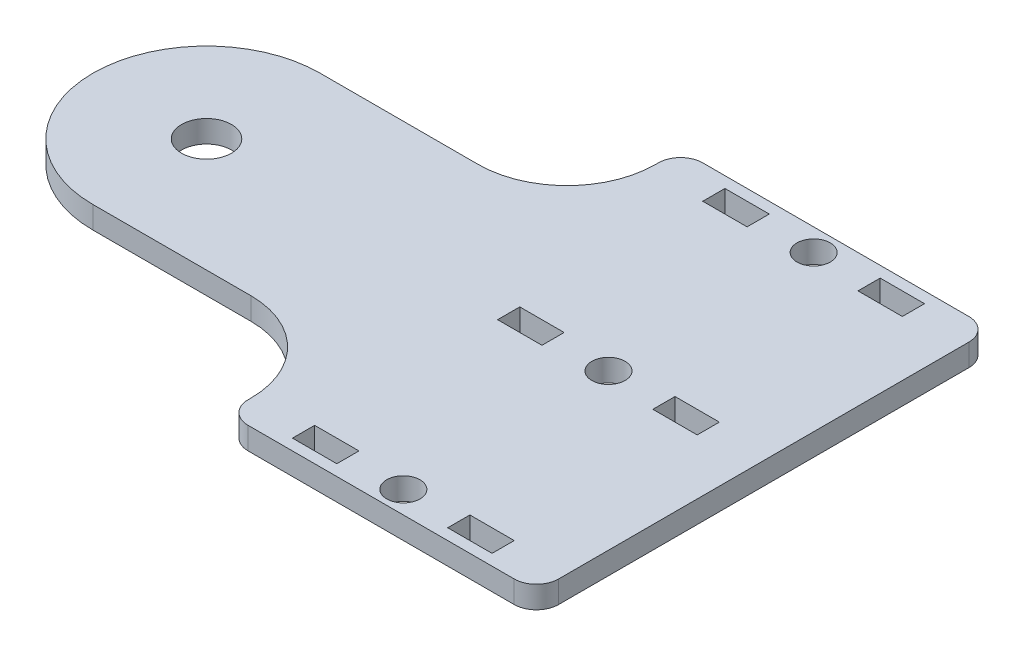
SolidWorks part; units mm, degrees
ref_plane "Front Plane" through (0, 0, 0) normal (0, 0, 1) x (1, 0, 0)
ref_plane "Top Plane" through (0, 0, 0) normal (0, 1, 0) x (1, 0, 0)
ref_plane "Right Plane" through (0, 0, 0) normal (1, 0, 0) x (0, 0, -1)
sketch "Sketch1" plane through (0, 0, 0) normal (0, 1, 0) x (1, 0, 0)
  line L0 (0, 10.25) -> (60.5, 10.25) construction
  line L1 (0, 0) -> (32.5, 0)
  line L2 (0, 0) -> (0, 20.5)
  line L3 (0, 20.5) -> (32.5, 20.5)
  line L4 (60.5, -0.75) -> (60.5, 21.25)
  line L5 (10.25, 10.25) -> (10.25, 20.5) construction
  line L8 (32.5, 0) -> (32.5, -10.25)
  line L10 (60.5, 21.25) -> (60.5, 30.75)
  line L11 (60.5, 30.75) -> (32.5, 30.75)
  line L12 (32.5, 20.5) -> (32.5, 30.75)
  line L13 (60.5, -10.25) -> (32.5, -10.25)
  line L14 (60.5, -0.75) -> (60.5, -10.25)
  circle A0 centre (10.25, 10.25) radius 2.25
  dimension "D3" = 4.5
  dimension "D4" = 20.5
  dimension "D5" = 10.25
  dimension "D6" = 50.25
  dimension "D7" = 41
  dimension "D8" = 28
extrude "Boss-Extrude1" add sketch "Sketch1" along normal blind 2
fillet "Fillet1" radius 10.25 2 edges at (0, 1, -20.5) (0, 1, 0)
fillet "Fillet2" radius 2 4 edges at (32.5, 1, -30.75) (60.5, 1, -30.75) (60.5, 1, 10.25) (32.5, 1, 10.25)
sketch "Sketch2" plane through (0, 2, 0) normal (0, 1, 0) x (1, 0, 0)
  line L0 (60.5, 10.25) -> (0, 10.25) construction
  line L1 (60.5, -8.25) -> (60.5, 28.75) construction
  line L2 (32.5, 28.75) -> (60.5, 28.75) construction
  line L3 (32.5, 28.75) -> (32.5, 20.5) construction
  line L15 (58.5, 30.75) -> (34.5, 30.75) construction
  line L17 (37.5, 27.75) -> (41.5, 27.75)
  line L18 (37.5, 27.75) -> (37.5, 29.75)
  line L19 (37.5, 29.75) -> (41.5, 29.75)
  line L20 (41.5, 27.75) -> (41.5, 29.75)
  line L21 (37.5, 27.75) -> (41.5, 29.75) construction
  line L22 (37.5, 29.75) -> (41.5, 27.75) construction
  line L23 (55.5, 27.75) -> (51.5, 27.75)
  line L24 (55.5, 27.75) -> (55.5, 29.75)
  line L25 (55.5, 29.75) -> (51.5, 29.75)
  line L26 (51.5, 27.75) -> (51.5, 29.75)
  line L27 (55.5, 27.75) -> (51.5, 29.75) construction
  line L28 (55.5, 29.75) -> (51.5, 27.75) construction
  line L37 (37.5, 9.25) -> (37.5, 11.25)
  line L38 (37.5, 9.25) -> (41.5, 9.25)
  line L39 (41.5, 9.25) -> (41.5, 11.25)
  line L40 (37.5, 11.25) -> (41.5, 11.25)
  line L41 (55.5, 9.25) -> (55.5, 11.25)
  line L42 (55.5, 9.25) -> (51.5, 9.25)
  line L43 (51.5, 9.25) -> (51.5, 11.25)
  line L44 (55.5, 11.25) -> (51.5, 11.25)
  line L53 (37.5, -9.25) -> (37.5, -7.25)
  line L54 (37.5, -9.25) -> (41.5, -9.25)
  line L55 (41.5, -9.25) -> (41.5, -7.25)
  line L56 (37.5, -7.25) -> (41.5, -7.25)
  line L57 (55.5, -9.25) -> (55.5, -7.25)
  line L58 (55.5, -9.25) -> (51.5, -9.25)
  line L59 (51.5, -9.25) -> (51.5, -7.25)
  line L60 (55.5, -7.25) -> (51.5, -7.25)
  circle A3 centre (46.5, 28.75) radius 1.5
  circle A4 centre (46.5, 10.25) radius 1.5
  circle A5 centre (46.5, -8.25) radius 1.5
  point P9 (26.5, 28.75)
  point P10 (53.5, 29.75)
  point P14 (35.5, 28.75)
  point P19 (39.5, 28.75)
  point P24 (53.5, 28.75)
  dimension "D11" = 3
  dimension "D12" = 5
  dimension "D2" = 4
  dimension "D3" = 1
  dimension "D5" = 5
  dimension "D6" = 10
  dimension "D8" = 3
extrude "Cut-Extrude1" cut sketch "Sketch2" against normal blind 2
fillet "Fillet3" radius 8 2 edges at (32.5, 1, 0) (32.5, 1, -20.5)
